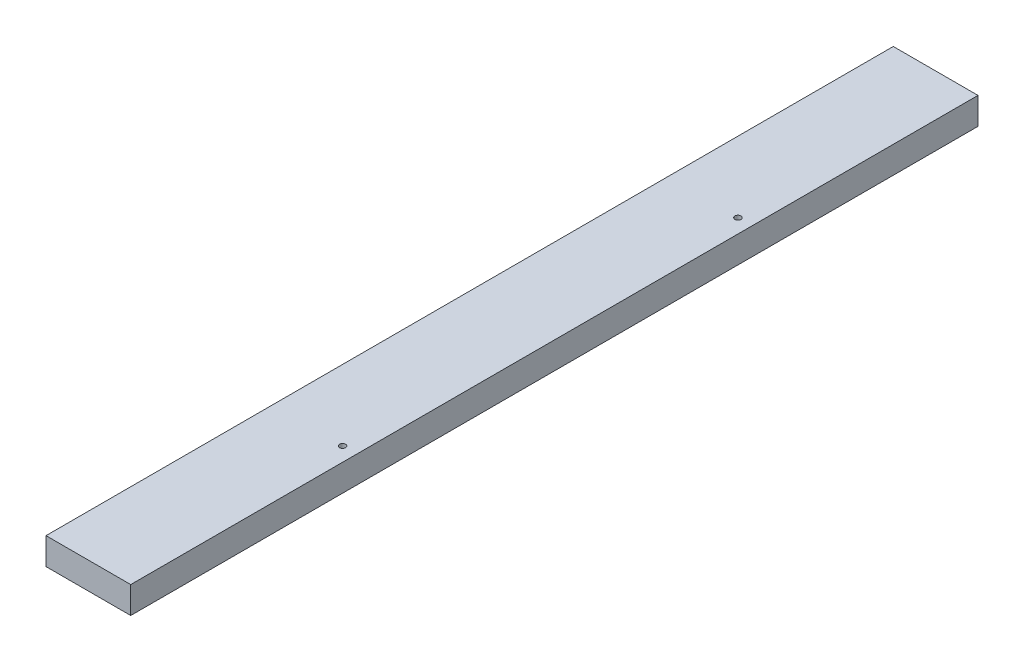
SolidWorks part; units mm, degrees
ref_plane "Płaszczyzna przednia" through (0, 0, 0) normal (0, 0, 1) x (1, 0, 0)
ref_plane "Płaszczyzna górna" through (0, 0, 0) normal (0, 1, 0) x (1, 0, 0)
ref_plane "Płaszczyzna prawa" through (0, 0, 0) normal (1, 0, 0) x (0, 0, -1)
sketch "Sketch1" plane through (0, 0, 0) normal (0, 0, 1) x (1, 0, 0)
  line L1 (0, 0) -> (60, 0)
  line L2 (0, 0) -> (0, 19)
  line L3 (0, 19) -> (60, 19)
  line L4 (60, 0) -> (60, 19)
  line L5 (0, 0) -> (60, 19) construction
  line L6 (0, 19) -> (60, 0) construction
  point P4 (30, 9.5)
  dimension "D1" = 19
  dimension "D2" = 60
extrude "Boss-Extrude1" add sketch "Sketch1" along normal blind 600
sketch "Sketch2" plane through (0, 0, 0) normal (0, -1, 0) x (-1, 0, 0)
  line L0 (0, 0) -> (-60, 0) construction
  line L1 (0, -600) -> (0, 0) construction
  line L2 (0, -600) -> (-60, -600) construction
  circle A0 centre (-38, -8) radius 2.5
  circle A1 centre (-38, -592) radius 2.5
  dimension "D1" = 8
  dimension "D2" = 38
  dimension "D3" = 5
  dimension "D4" = 5
  dimension "D5" = 8
  dimension "D6" = 38
extrude "Cut-Extrude1" cut sketch "Sketch2" against normal blind 10
sketch "Sketch3" plane through (0, 0, 0) normal (0, -1, 0) x (1, 0, 0)
  line L0 (47.1, 503.6529) -> (47.1, 502.5)
  line L1 (41.3, 550) -> (25.8, 550)
  line L2 (47.1, 543.5) -> (47.1, 503.6529)
  line L3 (47.1, 502.5) -> (20, 502.5)
  line L4 (20, 543.5) -> (20, 508.663)
  line L5 (47.1, 550) -> (20, 502.5) construction
  line L6 (47.1, 502.5) -> (20, 550) construction
  line L7 (20, 502.5) -> (20, 508.663)
  line L8 (0, 600) -> (0, 0) construction
  line L9 (25.8, 550) -> (20, 543.5)
  line L10 (0, 600) -> (60, 600) construction
  line L11 (47.1, 543.5) -> (41.3, 550)
  point P4 (33.55, 526.25)
  dimension "D1" = 47.5
  dimension "D2" = 27.1
  dimension "D3" = 5.8
  dimension "D4" = 6.5
  dimension "D5" = 5.8
  dimension "D6" = 6.5
  dimension "D7" = 20
  dimension "D8" = 50
extrude "Cut-Extrude2" [suppressed] cut sketch "Sketch3" against normal through all
sketch "Sketch4" [suppressed] plane through (0, 0, 0) normal (0, -1, 0) x (-1, 0, 0)
  line L0 (0, -600) -> (-60, -600) construction
  line L1 (-60, 0) -> (-60, -600) construction
  line L3 (0, -600) -> (0, 0) construction
  circle A0 centre (-53.55, -525.15) radius 1.8
  circle A1 centre (-13.55, -525.15) radius 1.8
  dimension "D1" = 3.6
  dimension "D2" = 3.6
  dimension "D3" = 74.85
  dimension "D4" = 74.85
  dimension "D5" = 6.45
  dimension "D6" = 13.55
extrude "Cut-Extrude3" [suppressed] cut sketch "Sketch4" against normal blind 13
hole_wizard "CSK for M4 Flat Head Machine Screw1" positions "Sketch6" profile "Sketch7" countersink size "M4" standard "ANSI Metric" end condition through all
sketch "Sketch6" plane through (0, 0, 0) normal (0, -1, 0) x (-1, 0, 0)
  line L0 (-60, -600) -> (-60, 0) construction
  line L2 (0, 0) -> (-60, 0) construction
  line L3 (0, -600) -> (-60, -600) construction
  point P0 (-50, -160)
  point P2 (-50, -440)
  point P11 (-26.056, 0)
  dimension "D1" = 10
  dimension "D2" = 160
  dimension "D3" = 10
  dimension "D4" = 160
sketch "Sketch7" plane through (50, 0, 160) normal (1, 0, 0) x (0, 0, -1)
  line L0 (0, 0) -> (0, 19)
  line L1 (0, 19) -> (2.15, 19)
  line L2 (2.15, 19) -> (2.15, 2.55)
  line L3 (2.15, 2.55) -> (4.7, 0)
  line L5 (4.7, 0) -> (0, 0)
  line L6 (-2.15, 2.55) -> (-4.7, 0) construction
  line L11 (0, -6.35) -> (0, 107.95) construction
  dimension "Thru Hole Dia." = 4.3
  dimension "Thru Hole Depth" = 19
  dimension "Near C'Sink Dia." = 9.4
  dimension "Near C'Sink Angle" = 90
